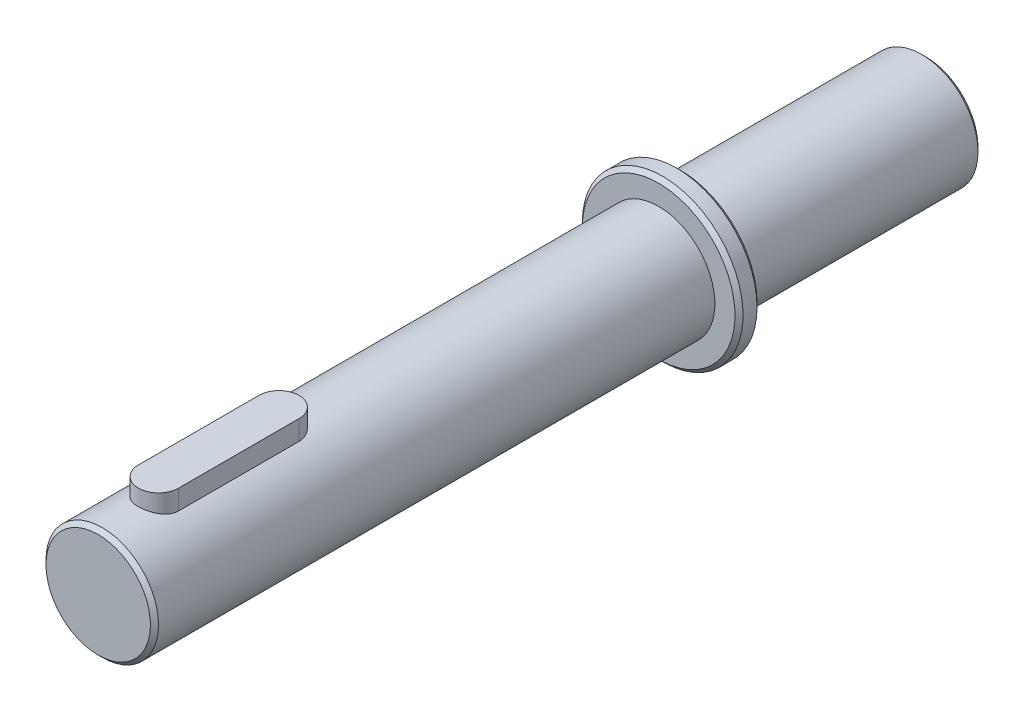
SolidWorks part; units mm, degrees
material "1.0038 (S235JRG2)"
ref_plane "Horní rovina" through (0, 0, 0) normal (0, 0, 1) x (1, 0, 0)
ref_plane "Přední rovina" through (0, 0, 0) normal (0, 1, 0) x (1, 0, 0)
ref_plane "Pravá rovina" through (0, 0, 0) normal (1, 0, 0) x (0, 0, -1)
sketch "Skica1" plane through (0, 0, 0) normal (0, 0, 1) x (1, 0, 0)
  circle A0 centre (0, 0) radius 7
  dimension "D1" = 14
extrude "Přidat vysunutím1" add sketch "Skica1" along normal blind 103
sketch "Skica2" plane through (0, 0, 0) normal (0, 1, 0) x (1, 0, 0)
  line L0 (7, 0) -> (-7, 0) construction
  line L1 (5, -30.5) -> (10, -30.5)
  line L2 (5, -30.5) -> (5, -33.25)
  line L3 (5, -33.25) -> (10, -33.25)
  line L4 (10, -30.5) -> (10, -33.25)
  line L5 (5, -30.5) -> (10, -33.25) construction
  line L6 (5, -33.25) -> (10, -30.5) construction
  line L7 (0, 0) -> (0, -50.9553) construction
  point P0 (7.5, -31.875)
  dimension "D1" = 2.75
  dimension "D2" = 5
  dimension "D3" = 30.5
  dimension "D4" = 10
revolve "Rotovat1" add sketch "Skica2" angle 360 about L7
chamfer "Zkosení1" distance 0.5 angle 45 4 edges at (7, 0, 103) (7, 0, 0) (-10, 0, 30.5) (-10, 0, 33.25)
ref_plane "Rovina1" through (0, 7, 0) normal (0, 1, 0) x (1, 0, 0)
sketch "Skica5" plane through (0, 7, 0) normal (0, 1, 0) x (1, 0, 0)
  line L0 (0, 0) -> (0, -122.2831) construction
  line L1 (0, -80.5) -> (0, -95.5) construction
  line L2 (-6.5, -103) -> (6.5, -103) construction
  line L3 (2.5, -80.5) -> (2.5, -95.5)
  line L4 (-2.5, -80.5) -> (-2.5, -95.5)
  arc A0 (2.5, -80.5) -> (-2.5, -80.5) centre (0, -80.5) ccw
  arc A1 (-2.5, -95.5) -> (2.5, -95.5) centre (0, -95.5) ccw
  point P7 (0, -88)
  dimension "D2" = 2.5
  dimension "D3" = 7.5
  dimension "D1" = 15
extrude "Přidat vysunutím2" add sketch "Skica5" along normal blind 2 and the other way blind 2
